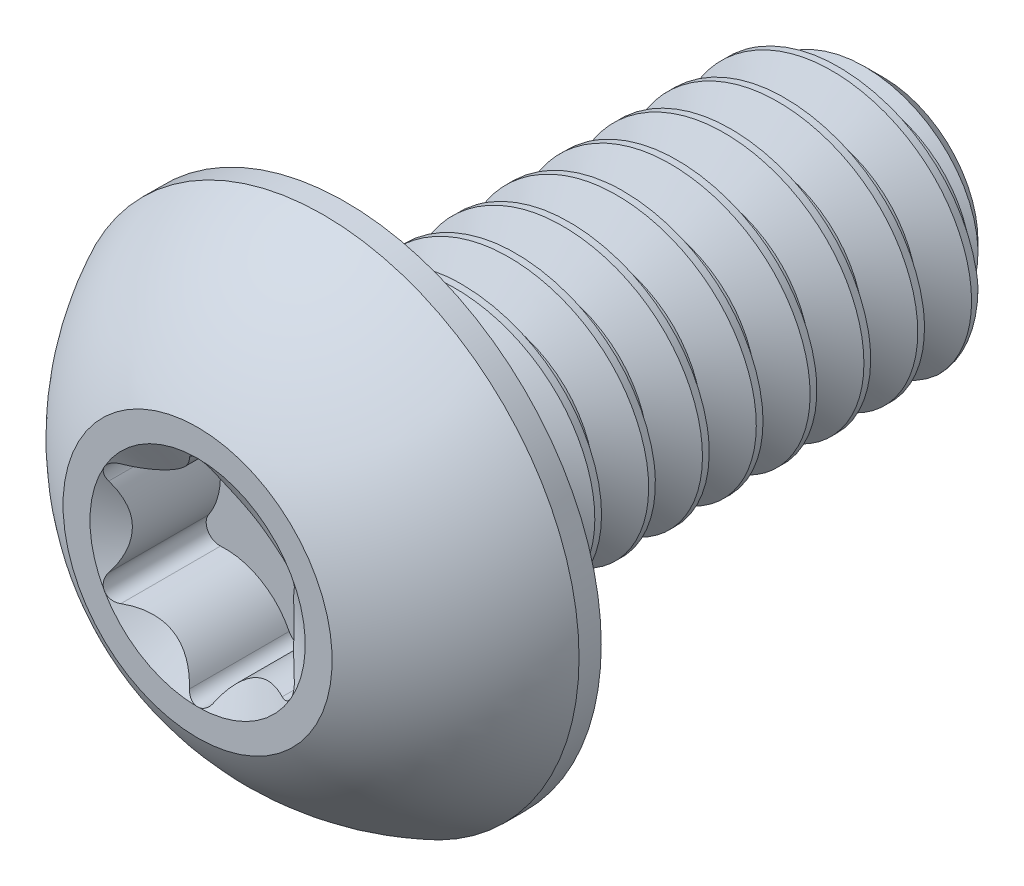
SolidWorks part; units mm, degrees
ref_plane "Front" through (0, 0, 0) normal (0, 0, 1) x (1, 0, 0)
ref_plane "Top" through (0, 0, 0) normal (0, 1, 0) x (1, 0, 0)
ref_plane "Right" through (0, 0, 0) normal (1, 0, 0) x (0, 0, -1)
sketch "Sketch1" plane through (0, 0, 0) normal (1, 0, 0) x (0, 0, -1)
  line L2 (1.1, 1) -> (5.1, 1)
  line L3 (5.1, 1) -> (5.1, 0)
  line L4 (5.1, 0) -> (1.1, 0)
  line L6 (0.935, 1.9) -> (1.1, 1.9) construction
  line L7 (5.1, 1) -> (5.1, -1) construction
  line L8 (0, 0) -> (1.1, 0) construction
  line L9 (1.1, 1.9) -> (1.1, -1.9) construction
  line L11 (1.1, 1) -> (1.1, 0)
  line L14 (0, 0) -> (0, 1) construction
  arc A3 (0, 1) -> (0.935, 1.9) centre (1.8632, 0) cw construction
  dimension "D1" = 0.165
  dimension "Head Ht" = 1.1
  dimension "Head Dia" = 3.8
  dimension "Dia" = 2
  dimension "Lg" = 4
revolve "Revolve1" add sketch "Sketch1" angle 360 mid plane about L4
sketch "Sketch3" plane through (0, 0, -5.1) normal (0, 0, -1) x (-1, 0, 0)
  circle A0 centre (0, 0) radius 1
curve "Helix/Spiral1" pitch 0.4 height 4.4 radius 1 centre (0, 0, -5.1) axis (0, 0, 1) start towards (0, 1, 0)
sketch "Sketch2" plane through (0, 0, 0) normal (1, 0, 0) x (0, 0, -1)
  line L0 (5.1, 1) -> (5.45, 1)
  line L1 (5.45, 1) -> (5.3, 0.7402)
  line L2 (5.3, 0.7402) -> (5.25, 0.7402)
  line L3 (5.25, 0.7402) -> (5.1, 1)
  line L4 (5.175, 0.8701) -> (5.375, 0.8701) construction
  dimension "D1" = 60
  dimension "D2" = 0.05
  dimension "D3" = 0.2
chamfer "Chamfer1" distance 0.3 angle 45 1 edges at (0, 1, -5.1)
sweep "Cut-Sweep1" cut profiles "Sketch2" path "Helix/Spiral1" align with end faces yes
sketch "Sketch7" plane through (0, 0, 0) normal (1, 0, 0) x (0, 0, -1)
  line L0 (0, 0) -> (0, 1) construction
  line L6 (0.935, 1.9) -> (1.1, 1.9) construction
  line L8 (0, 0) -> (1.1, 0) construction
  line L11 (1.1, 1.9) -> (1.1, -1.9) construction
  line L12 (0.935, 1.9) -> (1.1, 1.9)
  line L13 (0, 0) -> (1.1, 0)
  line L15 (1.1, 1.9) -> (1.1, 0)
  line L16 (0, 1) -> (0, 0)
  arc A2 (0.935, 1.9) -> (0, 1) centre (1.8632, 0) ccw construction
  arc A3 (0.935, 1.9) -> (0, 1) centre (1.8632, 0) ccw
revolve "Revolve2" add sketch "Sketch7" angle 360 mid plane about L13
sketch "Sketch5" plane through (0, 0, 0) normal (0, 0, 1) x (1, 0, 0)
  line L0 (2.6125, 0) -> (-2.6125, 0) construction
  line L2 (0, 0) -> (-0.6928, 0.4)
  line L3 (0, 0) -> (-0.6928, -0.4)
  line L4 (0, 0.8) -> (0, 0.7) construction
  line L5 (0, 0.7) -> (0, 0.6) construction
  circle A0 centre (0, 0) radius 0.6 construction
  circle A1 centre (0, 0) radius 0.7 construction
  circle A2 centre (0, 0) radius 0.8 construction
  arc A3 (-0.6894, 0.2944) -> (-0.6894, -0.2944) centre (-1.1298, 0) cw
  arc A4 (-0.6894, 0.2944) -> (-0.6928, 0.4) centre (-0.6062, 0.35) cw
  arc A5 (-0.6894, -0.2944) -> (-0.6928, -0.4) centre (-0.6062, -0.35) ccw
  dimension "D2" = 1.6
  dimension "D4" = 1.2
  dimension "D1" = 30
extrude "Cut-Extrude2" cut sketch "Sketch5" against normal blind 0.77
pattern_circular "CirPattern1" count 6 over 360 of "Cut-Extrude2"
sketch "Sketch11" plane through (0, 0, 0) normal (0, 0, 1) x (1, 0, 0)
  circle A0 centre (0, 0) radius 0.8 construction
  circle A1 centre (0, 0) radius 0.8
extrude "Cut-Extrude3" cut sketch "Sketch11" against normal blind 0.77 draft 60
sketch "Sketch9" [suppressed] plane through (0, 0, -1.4986) normal (0, 0, 1) x (1, 0, 0)
  circle A2 centre (0, 0) radius 1.4224
extrude "Boss-Extrude2" [suppressed] add sketch "Sketch9" against normal offset from surface (7.0104 mm away) 31.75 up to face at (0, 0.7, -5.1)
sketch "Sketch10" plane through (0, 0, 0) normal (1, 0, 0) x (0, 0, -1)
  line L0 (5.1, 1) -> (5.1, -1) construction
  point P0 (4.5, -1)
  dimension "D1" = 0.6
equation "\"D3@Helix/Spiral1\" = \"Lg@Sketch1\" + \"D4@Helix/Spiral1\""
equation "\"D2@Sketch2\" = \"D4@Helix/Spiral1\" * .125"
equation "\"D3@Sketch2\" = \"D4@Helix/Spiral1\" * .5"
equation "\"D1@Chamfer1\" = \"D4@Helix/Spiral1\" * .75"
equation "\"D1@Cut-Extrude2\" = \"Head Ht@Sketch1\" * .7"
equation "\"D1@Sketch1\" = \"Head Ht@Sketch1\" * .15"
equation "\"D1@Sketch10\" = \"D4@Helix/Spiral1\" * 1.5"
equation "\"D1@Cut-Extrude3\" = \"D1@Cut-Extrude2\""
equation "\"D2@Sketch5\" = \"Dia@Sketch1\" * .8"
equation "\"D4@Sketch5\" = \"D2@Sketch5\" * .75"
